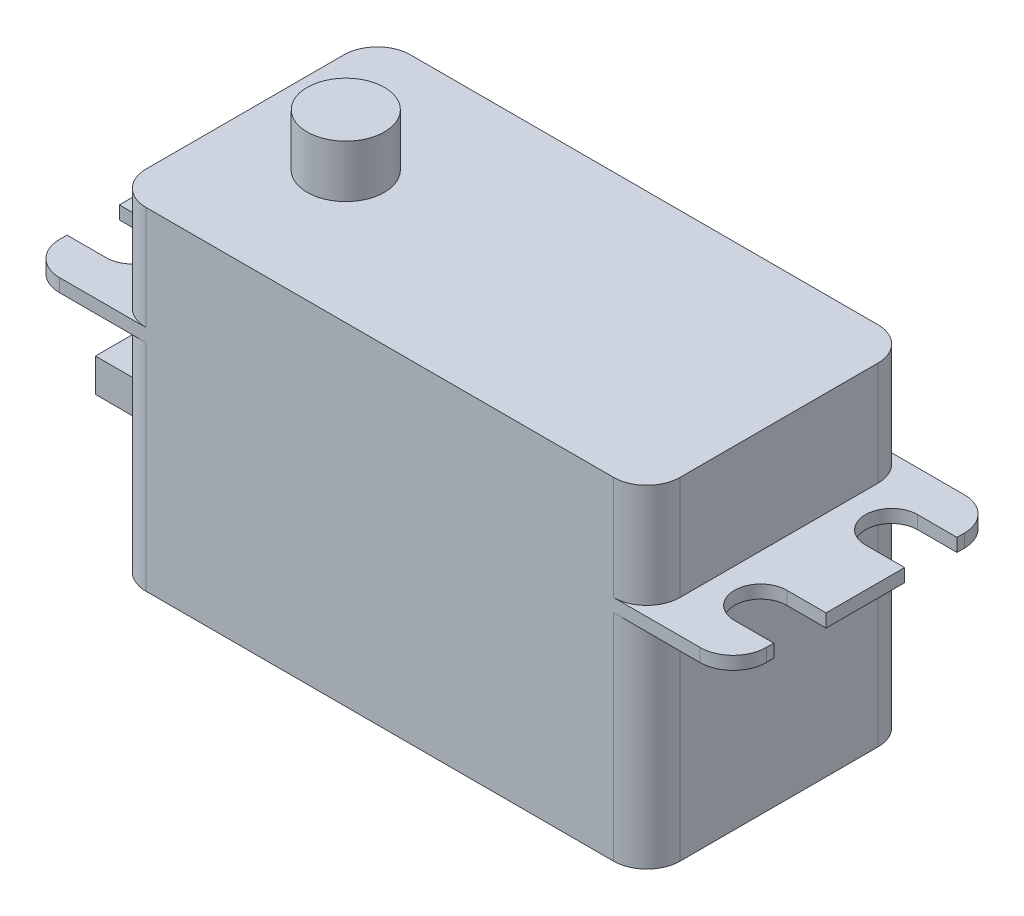
SolidWorks part; units mm, degrees
ref_plane "Front Plane" through (0, 0, 0) normal (0, 0, 1) x (1, 0, 0)
ref_plane "Top Plane" through (0, 0, 0) normal (0, 1, 0) x (1, 0, 0)
ref_plane "Right Plane" through (0, 0, 0) normal (1, 0, 0) x (0, 0, -1)
sketch "Sketch1" plane through (0, 0, 0) normal (0, 1, 0) x (1, 0, 0)
  line L0 (-16.17, 0) -> (16.17, 0) construction
  line L1 (-24.46, -10.1) -> (24.46, -10.1)
  line L2 (-27, -7.56) -> (-27, 7.56)
  line L3 (-24.46, 10.1) -> (24.46, 10.1)
  line L4 (27, -7.56) -> (27, 7.56)
  line L5 (-27, -10.1) -> (27, 10.1) construction
  line L6 (-27, 10.1) -> (27, -10.1) construction
  line L7 (0, -11.11) -> (0, 11.11) construction
  line L8 (24, 3) -> (27, 3)
  line L9 (24, 7) -> (27, 7)
  line L10 (27, 7) -> (27, 3)
  line L11 (24, -3) -> (27, -3)
  line L12 (24, -7) -> (27, -7)
  line L13 (27, -7) -> (27, -3)
  line L14 (-24, 7) -> (-27, 7)
  line L15 (-24, 3) -> (-27, 3)
  line L16 (-27, 3) -> (-27, 7)
  line L17 (-24, -7) -> (-27, -7)
  line L18 (-24, -3) -> (-27, -3)
  line L19 (-27, -3) -> (-27, -7)
  arc A0 (24, 7) -> (24, 3) centre (24, 5) ccw
  arc A1 (24, -7) -> (24, -3) centre (24, -5) cw
  arc A2 (-24, -7) -> (-24, -3) centre (-24, -5) ccw
  arc A3 (-24, 7) -> (-24, 3) centre (-24, 5) cw
  arc A4 (-24.46, -10.1) -> (-27, -7.56) centre (-24.46, -7.56) cw
  arc A5 (24.46, -10.1) -> (27, -7.56) centre (24.46, -7.56) ccw
  arc A6 (24.46, 10.1) -> (27, 7.56) centre (24.46, 7.56) cw
  arc A7 (-27, 7.56) -> (-24.46, 10.1) centre (-24.46, 7.56) cw
  point P0 (0, 0)
  dimension "D3" = 4
  dimension "D6" = 2.54
  dimension "D1" = 54
  dimension "D2" = 20.2
  dimension "D4" = 48
  dimension "D5" = 10
extrude "Boss-Extrude1" add sketch "Sketch1" along normal blind 1 contours A7 L2 L14 A3 L15 L18 A2 L17 A4 L1 A5 L4 L12 A1 L11 L8 A0 L9 A6 L3 region at (0, 0, 0)
sketch "Sketch3" plane through (0, 1, 0) normal (0, 1, 0) x (1, 0, 0)
  line L1 (-17.86, -10.1) -> (17.86, -10.1)
  line L2 (-20.4, -7.56) -> (-20.4, 7.56)
  line L3 (-17.86, 10.1) -> (17.86, 10.1)
  line L4 (20.4, -7.56) -> (20.4, 7.56)
  line L5 (-20.4, -10.1) -> (20.4, 10.1) construction
  line L6 (-20.4, 10.1) -> (20.4, -10.1) construction
  arc A0 (-17.86, -10.1) -> (-20.4, -7.56) centre (-17.86, -7.56) cw
  arc A1 (17.86, -10.1) -> (20.4, -7.56) centre (17.86, -7.56) ccw
  arc A2 (17.86, 10.1) -> (20.4, 7.56) centre (17.86, 7.56) cw
  arc A3 (-20.4, 7.56) -> (-17.86, 10.1) centre (-17.86, 7.56) cw
  point P0 (0, 0)
  dimension "D3" = 2.54
  dimension "D1" = 40.8
  dimension "D2" = 20.2
extrude "Boss-Extrude2" add sketch "Sketch3" along normal blind 7.95
sketch "Sketch4" plane through (0, 0, 0) normal (0, -1, 0) x (1, 0, 0)
  line L1 (-17.86, -10.1) -> (17.86, -10.1)
  line L2 (-20.4, -7.56) -> (-20.4, 7.56)
  line L3 (-17.86, 10.1) -> (17.86, 10.1)
  line L4 (20.4, -7.56) -> (20.4, 7.56)
  line L5 (-20.4, -10.1) -> (20.4, 10.1) construction
  line L6 (-20.4, 10.1) -> (20.4, -10.1) construction
  arc A0 (-17.86, -10.1) -> (-20.4, -7.56) centre (-17.86, -7.56) cw
  arc A1 (17.86, -10.1) -> (20.4, -7.56) centre (17.86, -7.56) ccw
  arc A2 (17.86, 10.1) -> (20.4, 7.56) centre (17.86, 7.56) cw
  arc A3 (-20.4, 7.56) -> (-17.86, 10.1) centre (-17.86, 7.56) cw
  point P0 (0, 0)
  dimension "D3" = 2.54
  dimension "D1" = 20.2
  dimension "D2" = 40.8
extrude "Boss-Extrude3" add sketch "Sketch4" along normal blind 16.45
sketch "Sketch5" plane through (-20.4, 0, 0) normal (-1, 0, 0) x (0, 0, 1)
  line L0 (-0.8843, -9.5287) -> (-0.8843, -11.2259)
  line L1 (-3.81, -11.6473) -> (3.81, -11.6473)
  line L2 (-3.81, -11.6473) -> (-3.81, -9.1073)
  line L3 (-3.81, -9.1073) -> (3.81, -9.1073)
  line L4 (3.81, -11.6473) -> (3.81, -9.1073)
  line L5 (-3.4243, -9.5287) -> (-1.6557, -9.5287)
  line L6 (-3.4243, -9.5287) -> (-3.4243, -11.2259)
  line L7 (-3.4243, -11.2259) -> (-1.6557, -11.2259)
  line L8 (-1.6557, -9.5287) -> (-1.6557, -11.2259)
  line L9 (-0.8843, -9.5287) -> (0.8843, -9.5287)
  line L10 (0.8843, -9.5287) -> (0.8843, -11.2259)
  line L11 (-0.8843, -11.2259) -> (0.8843, -11.2259)
  line L12 (1.6557, -9.5287) -> (1.6557, -11.2259)
  line L13 (1.6557, -9.5287) -> (3.4243, -9.5287)
  line L14 (3.4243, -9.5287) -> (3.4243, -11.2259)
  line L15 (1.6557, -11.2259) -> (3.4243, -11.2259)
  point P8 (0, -11.6473)
  point P18 (-3.4243, -10.3773)
  point P19 (-3.81, -10.3773)
  point P20 (0, -11.2259)
  dimension "D2" = 2.54
  dimension "D3" = 2.54
  dimension "D4" = 7.62
  dimension "D1" = 3
extrude "Boss-Extrude4" add sketch "Sketch5" along normal blind 7.62
sketch "Sketch6" plane through (0, 8.95, 0) normal (0, 1, 0) x (1, 0, 0)
  circle A0 centre (-12.7, 0) radius 2.95
  point P2 (-11.1359, 0)
  dimension "D1" = 5.9
  dimension "D2" = 12.7
extrude "Boss-Extrude5" add sketch "Sketch6" along normal blind 4
other "CPoint1" parameters "Diameter"=25.4, "StubLength"=38.1
ref_axis "Axis1" through (-38.02, -11.2259, -3.4243) along (1, 0, 0)
other "CPoint2" parameters "Diameter"=25.4, "StubLength"=38.1
ref_axis "Axis2" through (-38.02, -11.2259, -0.8843) along (1, 0, 0)
other "CPoint3" parameters "Diameter"=25.4, "StubLength"=38.1
ref_axis "Axis3" through (-38.02, -11.2259, 1.6557) along (1, 0, 0)
equation "\"Bodytube_OD\" = 6.17in"
equation "\"Bodytube_ID\" = 5.998in"
equation "\"Motor_OD\" = 4in"
equation "\"Fwd_Tube_Length\" = 40in"
equation "\"Mid_Tube_Length\" = 1in"
equation "\"Aft_Section_Length\"= 39in"
equation "\"AB_Coupler_OD_Length\"= 1in"
equation "\"AB_Coupling_Section_Length\"= 0.375in"
equation "\"AB_Coupler_Length\"= \"AB_Coupler_OD_Length\" + \"AB_Coupling_Section_Length\" * 2"
equation "\"Cutout_Angle\" = 80"
equation "\"AB_Paddle_Height\" = 0.375in"
equation "\"AB_Coupler_Num_Screws\"= 6"
equation "\"Num_Cutouts\" = 3"
equation "\"AB_Coupler_OD\"= 6.17in"
equation "\"AB_Coupler_ID\"= 5.75in"
equation "\"AB_Coupler_Surface_Diameter\"= 5.998in"
equation "\"AB_Coupling_Screw_Diameter\"= 0.1065in"
equation "\"AB_Central_Bushing_Length\" = .75in"
equation "\"Lead_Screw_Dist\" = 2.25in"
equation "\"Lead_Screw_Diam\" = 11mm"
equation "\"Paddle_Pin_Offset\" = .25in"
equation "\"Paddle_Pin_Radius\" = 2.25in"
equation "\"Paddle_Gear_OD\" = 3.2in"
equation "\"Drive_Gear_OD\" = 1.7in"
equation "\"Fwd_BKHD_From_Top\" = 18in"
equation "\"Fin_Thickness\"= .118in"
equation "\"Guiderail_Cutout_Diameter\"= 1.5in"
equation "\"DB9_Hole_Dist\" = 25mm"
equation "\"Airbrakes_Wire_Hole_Dia\" = .25in"
equation "\"Airbrakes_Wire_Hole_Dist\" = 1.1in"
equation "\"Servo_Gear_Offset\" = 0.5in"
equation "\"D2@Sketch6\"=\"Servo_Gear_Offset\""
